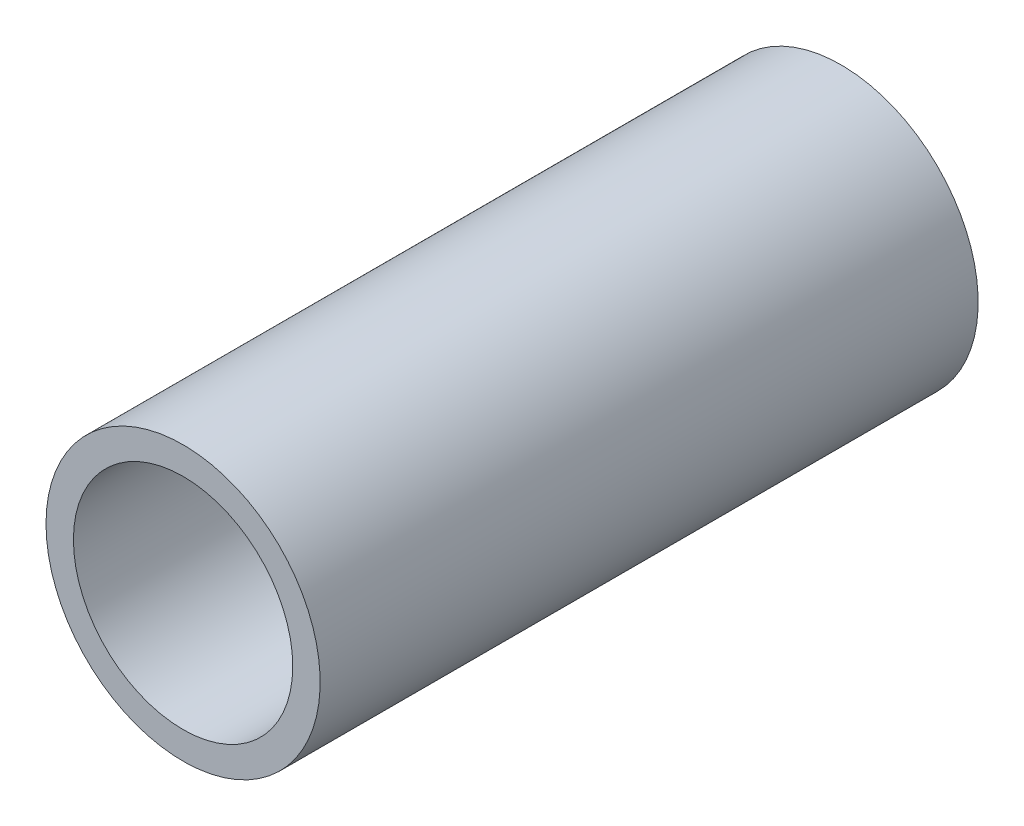
SolidWorks part; units mm, degrees
material "6061-T6 (SS)"
ref_plane "Plane1" through (0, 0, 0) normal (0, 0, 1) x (1, 0, 0)
ref_plane "Plane2" through (0, 0, 0) normal (0, 1, 0) x (1, 0, 0)
ref_plane "Plane3" through (0, 0, 0) normal (1, 0, 0) x (0, 0, -1)
ref_axis "Axis1" through (-80.9, 0, 0) along (1, 0, 0)
ref_axis "Axis2" through (0, 0, -80.9) along (0, 0, 1)
ref_axis "Axis3" through (0, 50, 0) along (0, -1, 0)
sketch "Sketch1" plane through (0, 0, 0) normal (0, 0, 1) x (1, 0, 0)
  circle A0 centre (0, 0) radius 3.9688
  circle A1 centre (0, 0) radius 3.175
  dimension "D1" = 6.35
  dimension "D2" = 7.9375
extrude "Boss-Extrude1" add sketch "Sketch1" along normal mid plane 19.05
